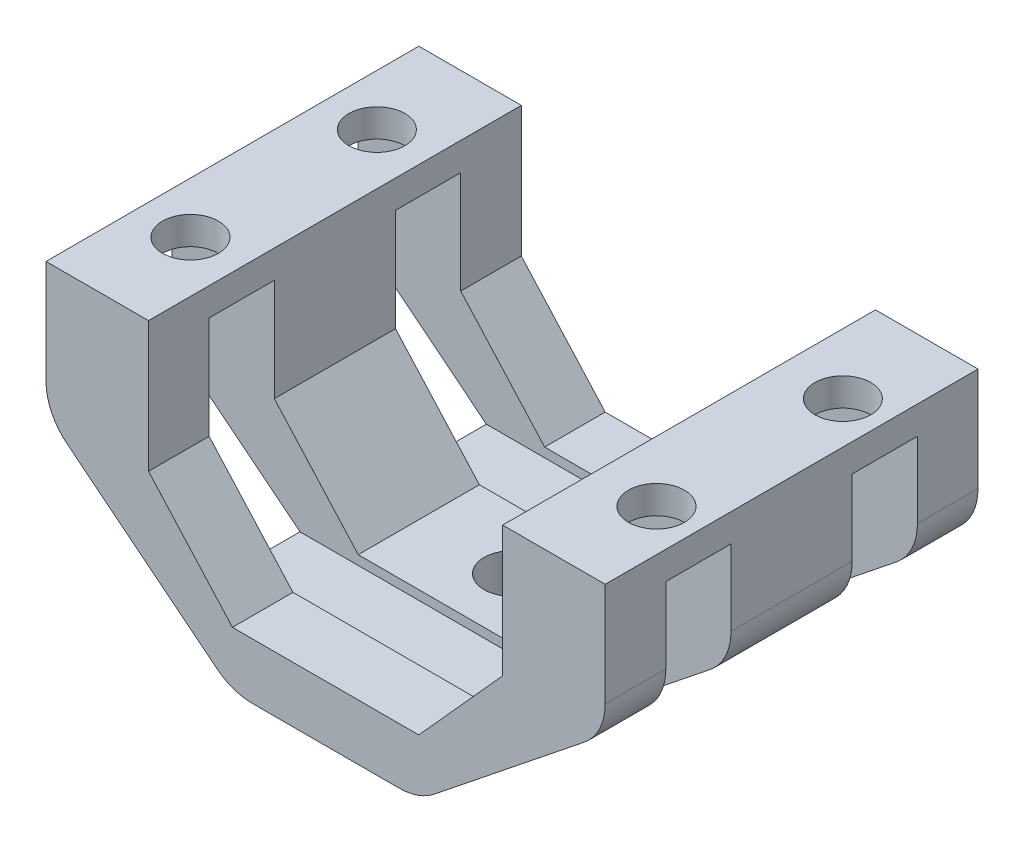
SolidWorks part; units mm, degrees
ref_plane "Alzado" through (0, 0, 0) normal (0, 0, 1) x (1, 0, 0)
ref_plane "Planta" through (0, 0, 0) normal (0, 1, 0) x (1, 0, 0)
ref_plane "Vista lateral" through (0, 0, 0) normal (1, 0, 0) x (0, 0, -1)
sketch "Croquis1" plane through (0, 0, 0) normal (0, 0, 1) x (1, 0, 0)
  line L0 (0, 0) -> (0, -5) construction
  line L21 (0, 0) -> (-4.5, 0) construction
  line L22 (-10, 0) -> (0, -8)
  line L23 (-4.5, 0) -> (-10, 0)
  line L24 (-4.5, 0) -> (-4.5, 7)
  line L25 (-4.5, 7) -> (-10, 7)
  line L26 (-10, 0) -> (-10, 7)
  line L27 (0, -5) -> (10, -5)
  line L28 (0, -5) -> (0, -8)
  line L29 (0, -8) -> (10, -8)
  line L30 (5, -5) -> (5, -8)
  line L31 (0, -5) -> (-4.5, 0)
  line L32 (10, -5) -> (10, -8)
  line L33 (20, 0) -> (10, -8)
  line L34 (10, -5) -> (14.5, 0)
  line L35 (14.5, 7) -> (20, 7)
  line L36 (20, 0) -> (20, 7)
  line L37 (14.5, 0) -> (20, 0)
  line L38 (14.5, 0) -> (14.5, 7)
  dimension "D1" = 7
  dimension "D2" = 4.5
  dimension "D3" = 5
  dimension "D4" = 3
  dimension "D5" = 5
  dimension "D6" = 5.5
extrude "Saliente-Extruir1" add sketch "Croquis1" along normal blind 20 contours L26 L23 L24 L25 | L28 L31 L23 L22 | L30 L27 L28 L29 | L32 L27 L30 L29 | L37 L34 L32 L33 | L38 L37 L36 L35 region at (-4.0507, -3.058, 0) region at (-7.25, 3.5, 0) region at (2.5, -6.5, 0) region at (7.5, -6.5, 0) region at (14.0507, -3.058, 0) region at (17.25, 3.5, 0)
sketch "Croquis2" plane through (-10, 0, 0) normal (-1, 0, 0) x (0, 0, 1)
  line L0 (10, 7) -> (10, 0) construction
  line L2 (20, 7) -> (0, 7) construction
  line L3 (20, 0) -> (0, 0) construction
  line L8 (0, 7) -> (10, 7) construction
  line L9 (5, 7) -> (5, 0) construction
  line L15 (16.75, 5.5) -> (13.25, 5.5)
  line L16 (3.25, -5.5) -> (6.75, -5.5)
  line L17 (3.25, -5.5) -> (3.25, 5.5)
  line L18 (3.25, 5.5) -> (6.75, 5.5)
  line L19 (6.75, -5.5) -> (6.75, 5.5)
  line L20 (3.25, -5.5) -> (6.75, 5.5) construction
  line L21 (3.25, 5.5) -> (6.75, -5.5) construction
  line L22 (13.25, -5.5) -> (13.25, 5.5)
  line L23 (16.75, -5.5) -> (13.25, -5.5)
  line L24 (16.75, -5.5) -> (16.75, 5.5)
  dimension "D1" = 3.5
  dimension "D2" = 1.5
extrude "Cortar-Extruir3" cut sketch "Croquis2" against normal through all
sketch "Croquis3" plane through (0, 7, 0) normal (0, 1, 0) x (1, 0, 0)
  line L0 (-7.25, 0) -> (-7.25, -5) construction
  line L1 (-4.5, 0) -> (-10, 0) construction
  circle A0 centre (-7.25, -5) radius 1.5
  circle A1 centre (17.75, -5) radius 1.5
  circle A2 centre (17.75, -15) radius 1.5
  circle A3 centre (-7.25, -15) radius 1.5
  dimension "D1" = 3
  dimension "D2" = 2
  dimension "D3" = 2
extrude "Cortar-Extruir4" cut sketch "Croquis3" against normal through all
fillet "Redondeo1" radius 3 8 edges at (10, -8, 10) (20, 0, 1.625) (20, 0, 18.375) (20, 0, 10) (0, -8, 10) (-10, 0, 18.375) (-10, 0, 1.625) (-10, 0, 10)
sketch "Croquis4" plane through (0, -5, 0) normal (0, 1, 0) x (1, 0, 0)
  line L0 (5, 0) -> (5, -20) construction
  line L1 (0, 0) -> (10, 0) construction
  line L2 (0, -20) -> (10, -20) construction
  circle A0 centre (5, -10) radius 1.5
extrude "Cortar-Extruir5" cut sketch "Croquis4" against normal through all
